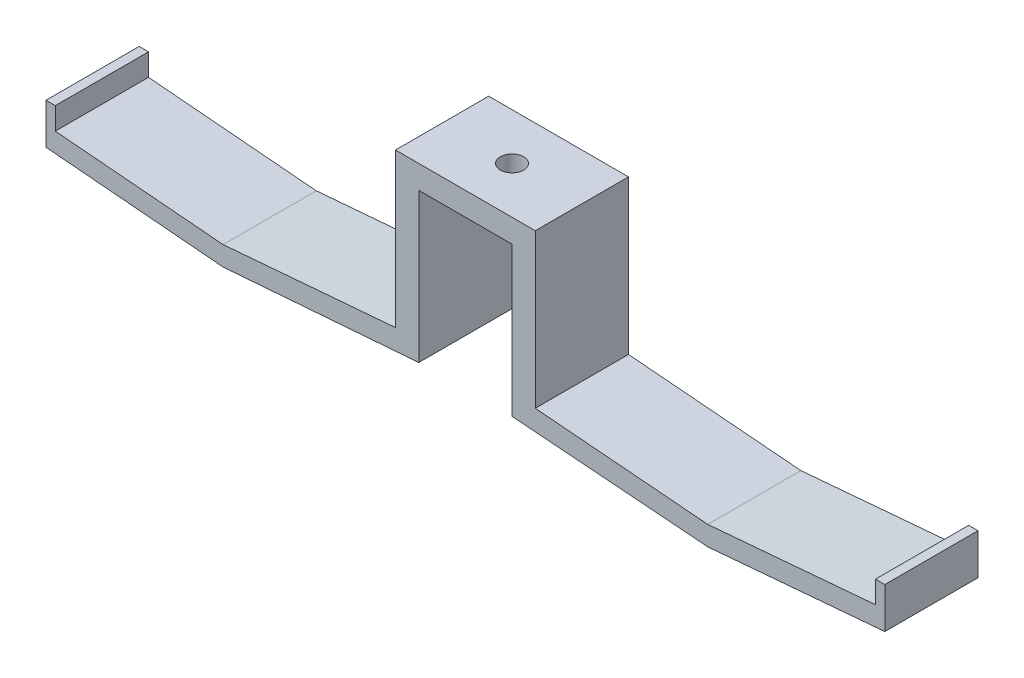
SolidWorks part; units mm, degrees
material "Nylon 6/10"
ref_plane "Front Plane" through (0, 0, 0) normal (0, 0, 1) x (1, 0, 0)
ref_plane "Top Plane" through (0, 0, 0) normal (0, 1, 0) x (1, 0, 0)
ref_plane "Right Plane" through (0, 0, 0) normal (1, 0, 0) x (0, 0, -1)
sketch "Sketch2" plane through (0, 0, 0) normal (0, 0, 1) x (1, 0, 0)
  line L1 (12.7, 0) -> (12.7, -40.64)
  line L2 (12.7, -40.64) -> (66.04, -44.7734)
  line L3 (66.04, -44.7734) -> (114.3, -40.64)
  line L4 (114.3, -40.64) -> (114.3, -29.5334)
  line L5 (111.76, -29.5334) -> (111.76, -35.56)
  line L6 (111.76, -35.56) -> (66.04, -39.4758)
  line L19 (114.3, -29.5334) -> (111.76, -29.5334)
  line L20 (0, 125.2351) -> (0, -75.9356) construction
  line L21 (12.7, 0) -> (-12.7, 0)
  line L22 (0, 0) -> (0, 6.35)
  line L23 (19.05, 6.35) -> (-19.05, 6.35)
  line L24 (19.05, 6.35) -> (19.05, 0)
  line L25 (19.05, 0) -> (19.05, -35.56)
  line L26 (19.05, -35.56) -> (66.04, -39.4758)
  line L27 (-19.05, 0) -> (-19.05, -35.56)
  line L28 (-19.05, 6.35) -> (-19.05, 0)
  line L29 (-12.7, 0) -> (-12.7, -40.64)
  line L30 (-12.7, -40.64) -> (-66.04, -44.7734)
  line L31 (-66.04, -44.7734) -> (-114.3, -40.64)
  line L32 (-114.3, -40.64) -> (-114.3, -29.5334)
  line L33 (-114.3, -29.5334) -> (-111.76, -29.5334)
  line L34 (-111.76, -29.5334) -> (-111.76, -35.56)
  line L35 (-111.76, -35.56) -> (-66.04, -39.4758)
  line L36 (-19.05, -35.56) -> (-66.04, -39.4758)
  dimension "D1" = 19.05
  dimension "D2" = 12.7
  dimension "D3" = 35.56
  dimension "D4" = 3.9158
  dimension "D5" = 40.64
  dimension "D6" = 2.54
  dimension "D7" = 45.72
  dimension "D8" = 46.99
  dimension "D9" = 15.24
  dimension "D10" = 6.35
extrude "Boss-Extrude1" add sketch "Sketch2" along normal blind 25.4 contours L26 L25 L24 L23 L22 L21 L1 L2 L3 L4 L19 L5 L6 | L27 L36 L35 L34 L33 L32 L31 L30 L29 L21 L22 L23 L28 region at (6.35, 1.2521, 0) region at (-6.35, 1.2521, 0)
sketch "Sketch3" plane through (0, 6.35, 0) normal (0, 1, 0) x (1, 0, 0)
  line L0 (19.05, -12.7) -> (-19.05, -12.7) construction
  line L1 (19.05, -25.4) -> (19.05, 0) construction
  line L2 (-19.05, -25.4) -> (-19.05, 0) construction
  circle A0 centre (0, -12.7) radius 3.175
  dimension "D1" = 6.35
extrude "Cut-Extrude1" cut sketch "Sketch3" against normal up to next
